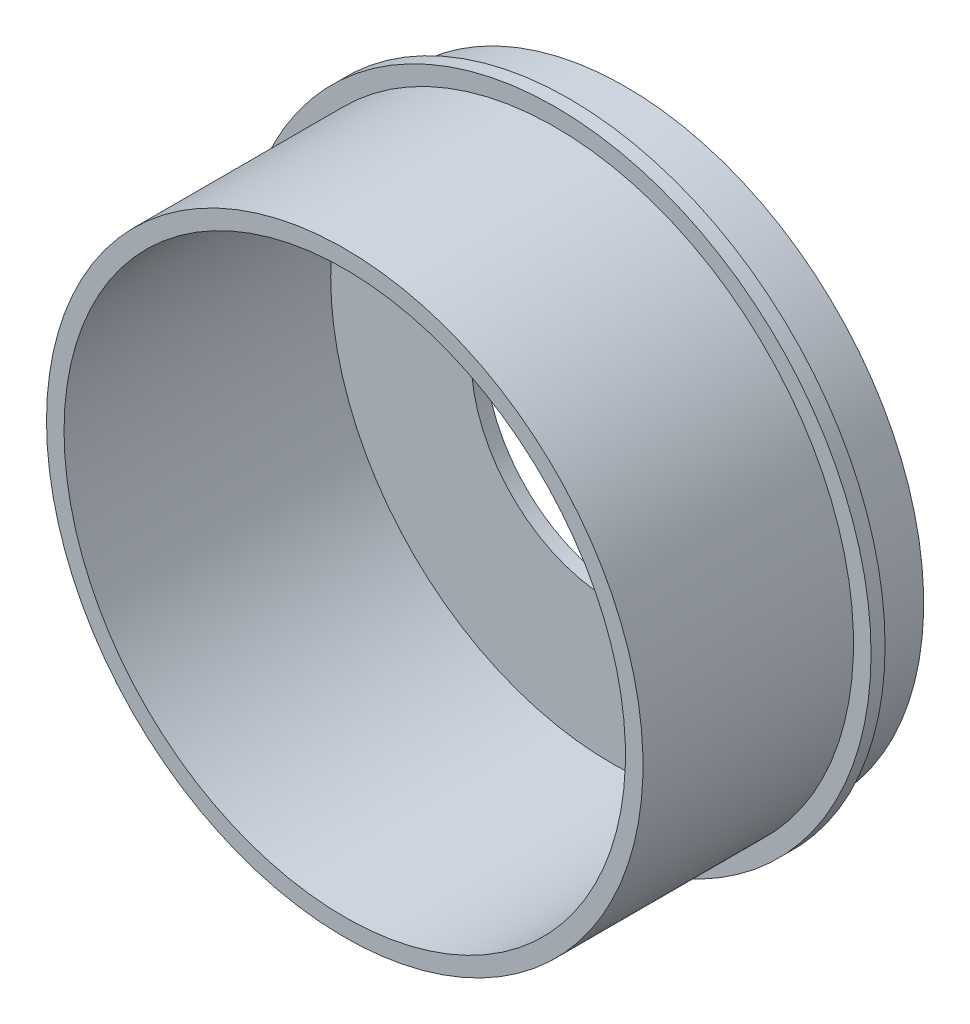
SolidWorks part; units mm, degrees
ref_plane "Front Plane" through (0, 0, 0) normal (0, 0, 1) x (1, 0, 0)
ref_plane "Top Plane" through (0, 0, 0) normal (0, 1, 0) x (1, 0, 0)
ref_plane "Right Plane" through (0, 0, 0) normal (1, 0, 0) x (0, 0, -1)
sketch "Sketch6" plane through (0, 0, 0) normal (1, 0, 0) x (0, 0, -1)
  line L0 (0, 0) -> (-40.103, 0) construction
  line L1 (0, 0) -> (0, 25.4) construction
  line L2 (0, 25.4) -> (-2.54, 25.4)
  line L3 (-2.54, 25.4) -> (-2.54, 50.8)
  line L4 (-2.54, 50.8) -> (-50.8, 50.8)
  line L5 (-50.8, 50.8) -> (-50.8, 53.975)
  line L6 (-50.8, 53.975) -> (-12.7, 53.975)
  line L7 (-12.7, 53.975) -> (-12.7, 57.15)
  line L8 (-12.7, 57.15) -> (-10.16, 57.15)
  line L9 (-10.16, 57.15) -> (-10.16, 53.975)
  line L10 (-10.16, 53.975) -> (0, 53.975)
  line L11 (0, 53.975) -> (0, 25.4)
  dimension "D1" = 28.575
  dimension "D2" = 25.4
  dimension "D3" = 50.8
  dimension "D4" = 48.26
  dimension "D5" = 3.175
  dimension "D6" = 3.175
  dimension "D7" = 2.54
  dimension "D8" = 38.1
revolve "Revolve1" add sketch "Sketch6" angle 360 about L0
